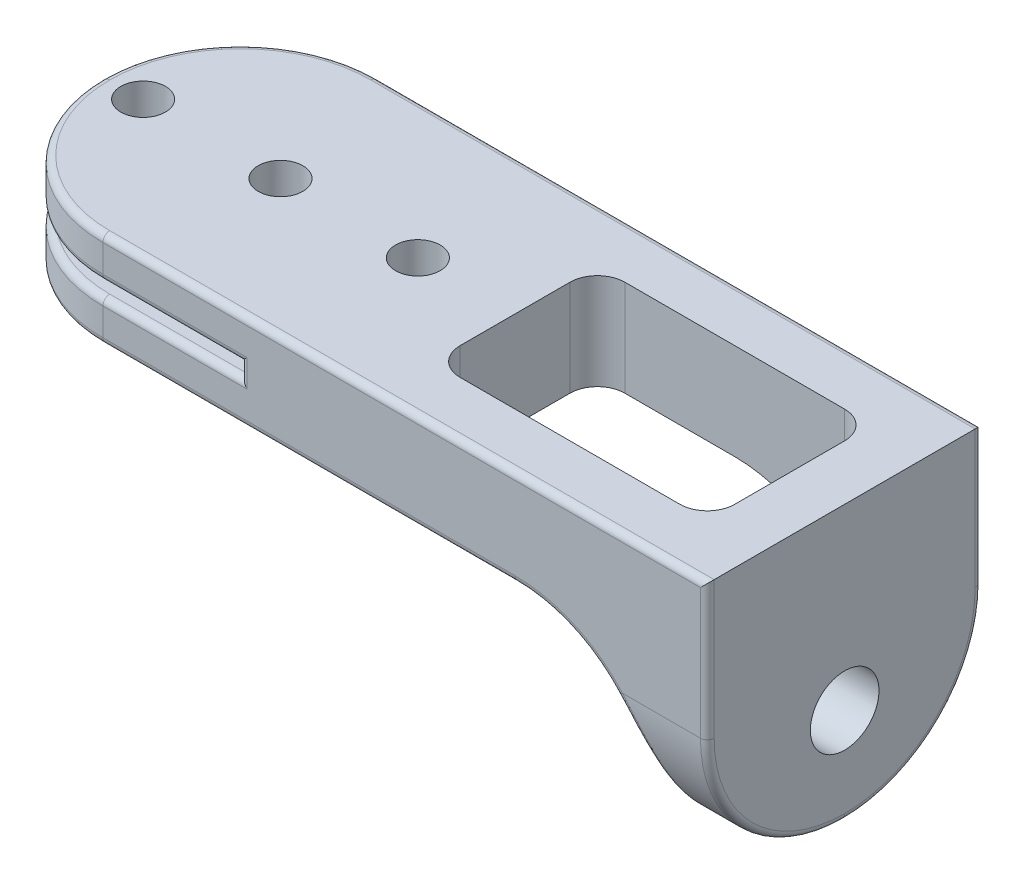
SolidWorks part; units mm, degrees
material "ABS"
ref_plane "Front Plane" through (0, 0, 0) normal (0, 0, 1) x (1, 0, 0)
ref_plane "Top Plane" through (0, 0, 0) normal (0, 1, 0) x (1, 0, 0)
ref_plane "Right Plane" through (0, 0, 0) normal (1, 0, 0) x (0, 0, -1)
sketch "Sketch1" plane through (0, 0, 0) normal (0, 0, 1) x (1, 0, 0)
  line L0 (0, 0) -> (0, -20)
  line L1 (0, -20) -> (-4, -20)
  line L2 (-4, -20) -> (-4, -7)
  line L3 (-4, -7) -> (-54, -7)
  line L4 (-54, -7) -> (-54, -4)
  line L5 (-54, -4) -> (-34, -4)
  line L6 (-34, -4) -> (-34, -3)
  line L7 (-34, -3) -> (-54, -3)
  line L8 (-54, -3) -> (-54, 0)
  line L9 (-54, 0) -> (0, 0)
  dimension "D1" = 4
  dimension "D2" = 20
  dimension "D3" = 50
  dimension "D4" = 3
  dimension "D5" = 1
  dimension "D6" = 20
extrude "Boss-Extrude1" add sketch "Sketch1" along normal mid plane 20
fillet "Fillet1" radius 10 4 edges at (-54, -5.5, -10) (-54, -1.5, -10) (-54, -5.5, 10) (-54, -1.5, 10)
sketch "Sketch3" plane through (0, 0, 0) normal (0, 1, 0) x (1, 0, 0)
  line L0 (-51.0711, 7.0711) -> (-51.0711, -7.0711) construction
  line L1 (-51.0711, 0) -> (-31.0711, 0) construction
  arc A0 (-44, 10) -> (-54, 0) centre (-44, 0) ccw construction
  arc A1 (-54, 0) -> (-44, -10) centre (-44, 0) ccw construction
  circle A2 centre (-51.0711, 0) radius 1.625
  circle A3 centre (-41.0711, 0) radius 1.625
  circle A4 centre (-31.0711, 0) radius 1.625
  dimension "D1" = 3.25
  dimension "D2" = 20
extrude "Cut-Extrude1" cut sketch "Sketch3" against normal through all and the other way through all
fillet "Fillet2" radius 10 2 edges at (-2, -20, 10) (-2, -20, -10)
sketch "Sketch4" plane through (-4, 0, 0) normal (-1, 0, 0) x (0, 0, 1)
  line L0 (0, -20) -> (0, -13) construction
  circle A0 centre (0, -13) radius 2.5
  arc A2 (-10, -10) -> (0, -20) centre (0, -10) ccw construction
  arc A3 (0, -20) -> (10, -10) centre (0, -10) ccw construction
  point P12 (0, 0)
  dimension "D2" = 5
  dimension "D1" = 7
extrude "Cut-Extrude2" cut sketch "Sketch4" against normal through all
sketch "Sketch5" plane through (0, 0, 0) normal (0, 1, 0) x (1, 0, 0)
  line L5 (-24, 6) -> (-24, -6)
  line L7 (-4, 6) -> (-44, 6)
  line L8 (-44, -6) -> (-4, -6)
  line L9 (-4, -6) -> (-4, 6)
  line L10 (-4, 6) -> (-44, 6)
  line L11 (-44, -6) -> (-4, -6)
  line L12 (-4, -6) -> (-4, 6)
  arc A4 (-44, 6) -> (-50, 0) centre (-44, 0) ccw
  arc A5 (-50, 0) -> (-44, -6) centre (-44, 0) ccw
  arc A6 (-44, 6) -> (-50, 0) centre (-44, 0) ccw
  arc A7 (-50, 0) -> (-44, -6) centre (-44, 0) ccw
  dimension "D2" = 20
  dimension "D1" = 4
extrude "Cut-Extrude3" cut sketch "Sketch5" against normal through all contours L11 L12 L10 L5 region at (-14, 0, 0)
fillet "Fillet3" radius 10 2 edges at (-4, -7, -8) (-4, -7, 8)
fillet "Fillet5" radius 0.5 27 edges at (-39, -4, -10) (-51.0711, -4, -7.0711) (-51.0711, -4, 7.0711) (-39, -3, -10) (-51.0711, -3, -7.0711) (-51.0711, -3, 7.0711) (-22, 0, -10) (-51.0711, 0, -7.0711) (-51.0711, 0, 7.0711) (0, -5, -10) (0, -17.0711, -7.0711) (0, -17.0711, 7.0711) (-51.0711, -7, 7.0711) (-51.0711, -7, -7.0711) (-29, -7, -10) (-10.127, -7.7805, -10) (-5.0552, -12.5289, -9.675) (-4, -19.2195, -3.873) (-4, -19.2195, 3.873) (-4.325, -14.4711, 8.9448) (-39, -4, 10) (-34, -3.5, 10) (-39, -3, 10) (-22, 0, 10) (0, -5, 10) (-10.127, -7.7805, 10) (-29, -7, 10)
fillet "Fillet6" radius 2 4 edges at (-24, -3.5, 6) (-24, -3.5, -6) (-4, -8.5, -6) (-4, -8.5, 6)
